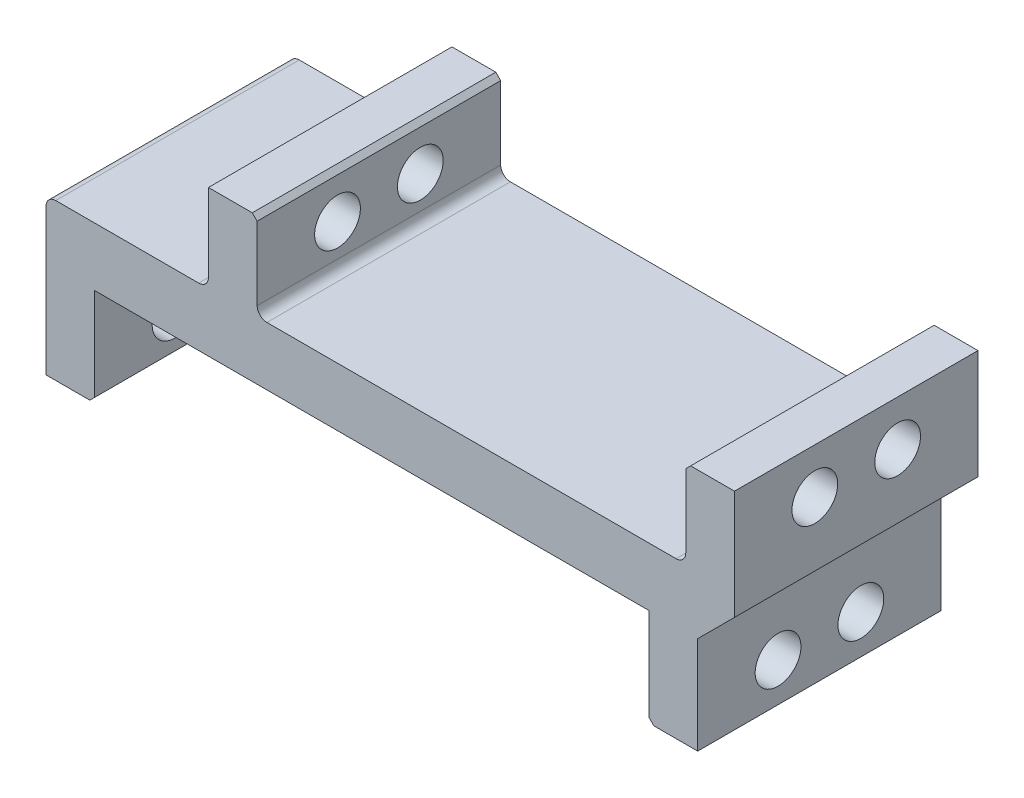
SolidWorks part; units mm, degrees
ref_plane "Front Plane" through (0, 0, 0) normal (0, 0, 1) x (1, 0, 0)
ref_plane "Top Plane" through (0, 0, 0) normal (0, 1, 0) x (1, 0, 0)
ref_plane "Right Plane" through (0, 0, 0) normal (1, 0, 0) x (0, 0, -1)
sketch "Sketch5" plane through (0, 0, 0) normal (0, 0, 1) x (1, 0, 0)
  line L1 (33.45, 0.7) -> (37.225, 4.475)
  line L3 (28.25, 0.5) -> (28.25, -43.5) construction
  line L4 (-28.25, 0.5) -> (28.25, 0.5) construction
  line L5 (-28.25, -43.5) -> (-28.25, 0.5) construction
  line L6 (-28.45, -9.3) -> (-28.45, 0.7)
  line L7 (-28.45, 0.7) -> (28.45, 0.7)
  line L8 (28.45, 0.7) -> (28.45, -9.3)
  line L9 (-28.45, -43.5) -> (-28.45, 0.7) construction
  line L10 (28.45, 0.7) -> (28.45, -43.5) construction
  line L11 (0, 0.7) -> (0, -12.0605) construction
  line L12 (-27.75, 0.5) -> (27.75, 0.5) construction
  line L13 (-28.45, -9.3) -> (-33.45, -9.3)
  line L14 (28.45, -9.3) -> (33.45, -9.3)
  line L15 (-33.45, -9.3) -> (-33.45, 5.7)
  line L16 (33.45, -9.3) -> (33.45, 0.7)
  line L17 (-32.45, 6.7) -> (-17.775, 6.7)
  line L19 (-16.775, 7.7) -> (-16.775, 15.7)
  line L20 (37.225, 4.475) -> (37.225, 15.7)
  line L21 (-16.775, 15.7) -> (-11.775, 15.7)
  line L22 (37.225, 15.7) -> (32.225, 15.7)
  line L23 (-11.775, 15.7) -> (-11.775, 7.7)
  line L24 (32.225, 15.7) -> (32.225, 7.7)
  line L25 (-10.775, 6.7) -> (31.225, 6.7)
  line L26 (10.225, -75) -> (10.225, -48.5) construction
  line L27 (-11.775, 11.7) -> (32.225, 11.7) construction
  line L28 (-28.25, -43.5) -> (-28.25, 0) construction
  line L29 (28.25, 0) -> (28.25, -43.5) construction
  arc A0 (-11.775, 7.7) -> (-10.775, 6.7) centre (-10.775, 7.7) ccw
  arc A1 (32.225, 7.7) -> (31.225, 6.7) centre (31.225, 7.7) cw
  arc A4 (-17.775, 6.7) -> (-16.775, 7.7) centre (-17.775, 7.7) ccw
  arc A5 (-33.45, 5.7) -> (-32.45, 6.7) centre (-32.45, 5.7) cw
  point P7 (-28.7933, 0.2)
  point P16 (0, 0)
  point P22 (34.1376, 0.2)
  point P31 (-11.775, 6.7)
  point P34 (10.225, 11.7)
  point P35 (-19.4829, 6.2)
  point P43 (0, 0)
  point P46 (-33.45, 6.7)
  point P50 (0, 0)
  point P51 (0, 0)
  point P53 (0, 0)
  point P54 (0, 0)
  dimension "D7" = 1
  dimension "D2" = 10
  dimension "D3" = 5
  dimension "D4" = 5
  dimension "D5" = 44
  dimension "D6" = 6
  dimension "D8" = 9
  dimension "D9" = 135
  dimension "D1" = 0.2
extrude "Boss-Extrude3" add sketch "Sketch5" along normal mid plane 25
sketch "Sketch6" plane through (0, 0, 0) normal (1, 0, 0) x (0, 0, -1)
  line L1 (-4.25, 11.05) -> (4.25, 11.05) construction
  line L2 (-4.25, 11.05) -> (-4.25, -5.3) construction
  line L3 (-4.25, -5.3) -> (4.25, -5.3) construction
  line L4 (4.25, 11.05) -> (4.25, -5.3) construction
  line L5 (-4.25, 11.05) -> (4.25, -5.3) construction
  line L6 (-4.25, -5.3) -> (4.25, 11.05) construction
  line L9 (-12.5, -9.3) -> (12.5, -9.3) construction
  line L13 (-12.5, 6.7) -> (12.5, 6.7) construction
  circle A0 centre (-4.25, 11.05) radius 2.35
  circle A1 centre (4.25, 11.05) radius 2.35
  circle A2 centre (4.25, -5.3) radius 2.35
  circle A3 centre (-4.25, -5.3) radius 2.35
  point P10 (0, 2.875)
  dimension "D1" = 4.7
  dimension "D4" = 2
  dimension "D2" = 8.5
  dimension "D3" = 4
extrude "Cut-Extrude1" cut sketch "Sketch6" against normal through all both and the other way through all
chamfer "Chamfer1" distance 0.5 angle 45 4 edges at (32.225, 15.7, 0) (-11.775, 15.7, 0) (28.45, -9.3, 0) (-28.45, -9.3, 0)
